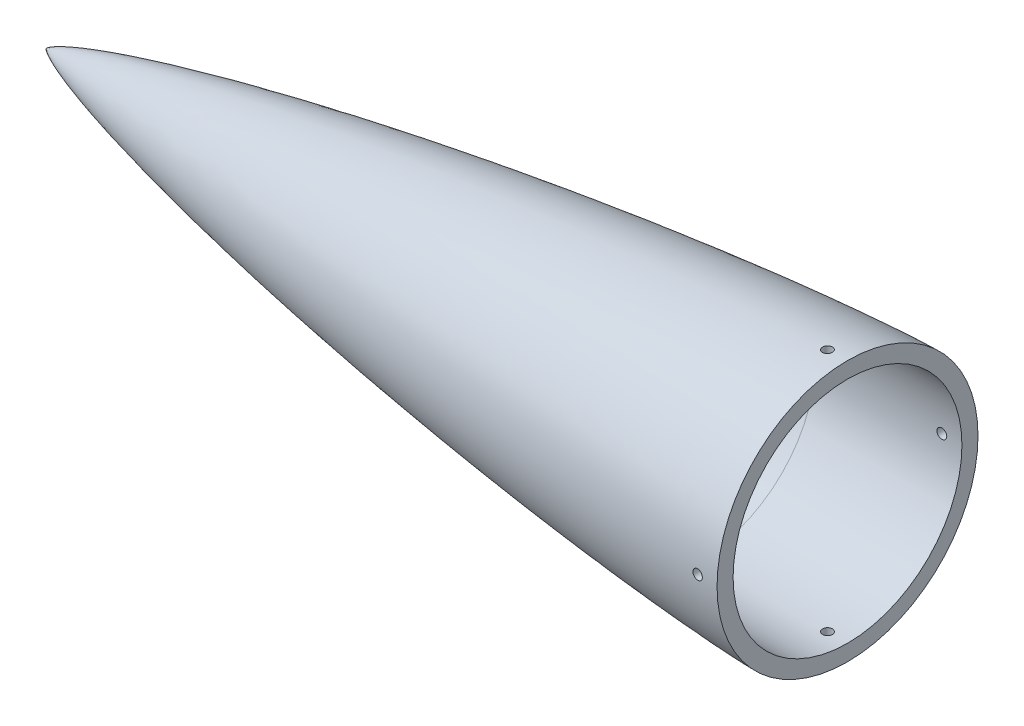
SolidWorks part; units mm, degrees
material "ABS"
ref_plane "Front Plane" through (0, 0, 0) normal (0, 0, 1) x (1, 0, 0)
ref_plane "Top Plane" through (0, 0, 0) normal (0, 1, 0) x (1, 0, 0)
ref_plane "Right Plane" through (0, 0, 0) normal (1, 0, 0) x (0, 0, -1)
sketch "Sketch1" plane through (0, 0, 0) normal (0, 0, 1) x (1, 0, 0)
  line L0 (-253.5034, 0) -> (0, 0)
  line L1 (0, 0) -> (0, 41.275)
  spline S0 degree 4 poles (-253.5034, 0) (-253.5001, 0.011) (-253.4914, 0.032) (-253.4658, 0.0703) (-253.4247, 0.1203) (-253.3747, 0.1726) (-253.3027, 0.2404) (-253.2023, 0.3261) (-253.0469, 0.446) (-252.7832, 0.6287) (-252.338, 0.9036) (-251.5539, 1.3319) (-250.1229, 2.0178) (-247.5507, 3.0885) (-243.2631, 4.6369) (-235.6289, 7.0412) (-224.7697, 9.992) (-211.2205, 13.2451) (-195.6313, 16.601) (-179.8348, 19.7095) (-163.9946, 22.5872) (-148.1196, 25.2651) (-132.215, 27.7612) (-116.2847, 30.0869) (-100.331, 32.2471) (-84.3559, 34.2424) (-68.3606, 36.0682) (-52.3456, 37.7135) (-36.3112, 39.1591) (-22.7463, 40.1808) (-12.4222, 40.8009) (-5.3475, 41.119) (-2.2922, 41.2225) (-0.7642, 41.2628) (0, 41.275) knots 0 0 0 0 0 0.000177 0.000355 0.000709 0.001004 0.001299 0.001888 0.002757 0.004048 0.006275 0.010003 0.016613 0.028658 0.049486 0.080709 0.140768 0.203215 0.265661 0.328107 0.390553 0.452999 0.515445 0.577892 0.640338 0.702784 0.76523 0.827676 0.890122 0.952569 0.976284 0.988142 1 1 1 1 1 construction
  spline S1 degree 4 poles (-253.5034, 0) (-253.5001, 0.011) (-253.4914, 0.032) (-253.4658, 0.0703) (-253.4247, 0.1203) (-253.3747, 0.1726) (-253.3027, 0.2404) (-253.2023, 0.3261) (-253.0469, 0.446) (-252.7832, 0.6287) (-252.338, 0.9036) (-251.5539, 1.3319) (-250.1229, 2.0178) (-247.5507, 3.0885) (-243.2631, 4.6369) (-235.6289, 7.0412) (-224.7697, 9.992) (-211.2205, 13.2451) (-195.6313, 16.601) (-179.8348, 19.7095) (-163.9946, 22.5872) (-148.1196, 25.2651) (-132.215, 27.7612) (-116.2847, 30.0869) (-100.331, 32.2471) (-84.3559, 34.2424) (-68.3606, 36.0682) (-52.3456, 37.7135) (-36.3112, 39.1591) (-22.7463, 40.1808) (-12.4222, 40.8009) (-5.3475, 41.119) (-2.2922, 41.2225) (-0.7642, 41.2628) (0, 41.275) knots 0 0 0 0 0 0.000177 0.000355 0.000709 0.001004 0.001299 0.001888 0.002757 0.004048 0.006275 0.010003 0.016613 0.028658 0.049486 0.080709 0.140768 0.203215 0.265661 0.328107 0.390553 0.452999 0.515445 0.577892 0.640338 0.702784 0.76523 0.827676 0.890122 0.952569 0.976284 0.988142 1 1 1 1 1
  dimension "D1" = 41.275
revolve "Revolve1" add sketch "Sketch1" angle 360 about L0
shell "Shell1" thickness 2.032 removed face at (0, -41.275, 0)
sketch "Sketch4" plane through (0, 0, 0) normal (0, 1, 0) x (1, 0, 0)
  line L0 (0, 36.195) -> (0, 41.275)
  line L1 (0, -41.275) -> (0, 41.275) construction
  line L2 (0, 41.275) -> (-63.5, 36.195)
  line L3 (-63.5, 36.195) -> (0, 36.195)
  point P4 (0, 38.7562)
  point P8 (0, 0)
  point P9 (0, 0)
  point P12 (0, 0)
  dimension "D1" = 36.195
  dimension "D2" = 63.5
ref_axis "Axis1" through (12.6752, 0, 0) along (-1, 0, 0)
revolve "Revolve2" add sketch "Sketch4" angle 360 about axis through (12.6752, 0, 0) along (-1, 0, 0)
sketch "Sketch5" plane through (0, 0, 0) normal (0, 1, 0) x (1, 0, 0)
  line L0 (12.6752, 0) -> (-266.1786, 0) construction
  line L1 (0, -36.195) -> (0, 36.195) construction
  circle A0 centre (-6.35, 0) radius 1.55
  dimension "D2" = 3.1
  dimension "D1" = 6.35
extrude "Cut-Extrude1" cut sketch "Sketch5" against normal through all both and the other way through all
pattern_circular "CirPattern1" count 2 every 90 about axis through (12.6752, 0, 0) along (-1, 0, 0) of "Cut-Extrude1"
